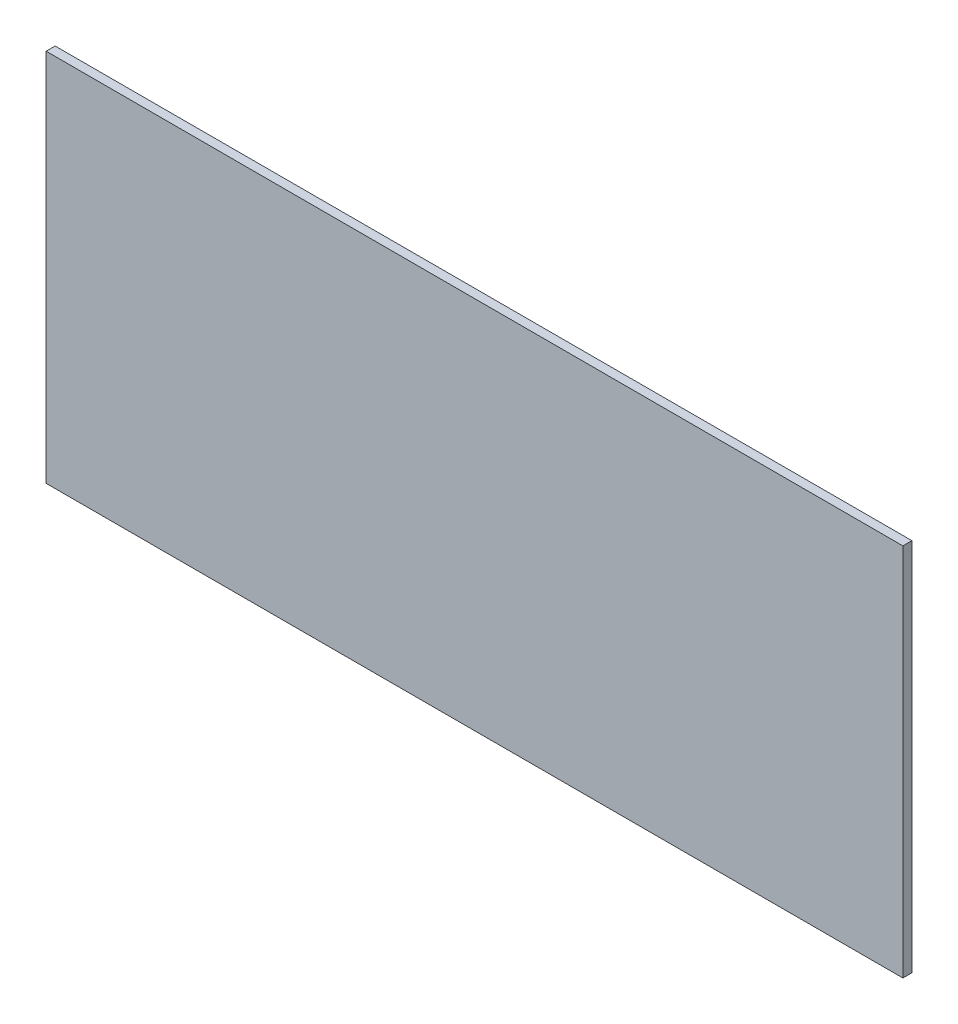
SolidWorks part; units mm, degrees
ref_plane "Plan de face" through (0, 0, 0) normal (0, 0, 1) x (1, 0, 0)
ref_plane "Plan de dessus" through (0, 0, 0) normal (0, 1, 0) x (1, 0, 0)
ref_plane "Plan de droite" through (0, 0, 0) normal (1, 0, 0) x (0, 0, -1)
sketch "Esquisse1" plane through (0, 0, 0) normal (0, 0, 1) x (1, 0, 0)
  line L1 (-208.4671, 52.8304) -> (171.5329, 52.8304)
  line L2 (-208.4671, 52.8304) -> (-208.4671, -113.1696)
  line L3 (-208.4671, -113.1696) -> (171.5329, -113.1696)
  line L4 (171.5329, 52.8304) -> (171.5329, -113.1696)
  dimension "D1" = 380
  dimension "D2" = 166
extrude "Boss.-Extru.1" add sketch "Esquisse1" along normal blind 4
